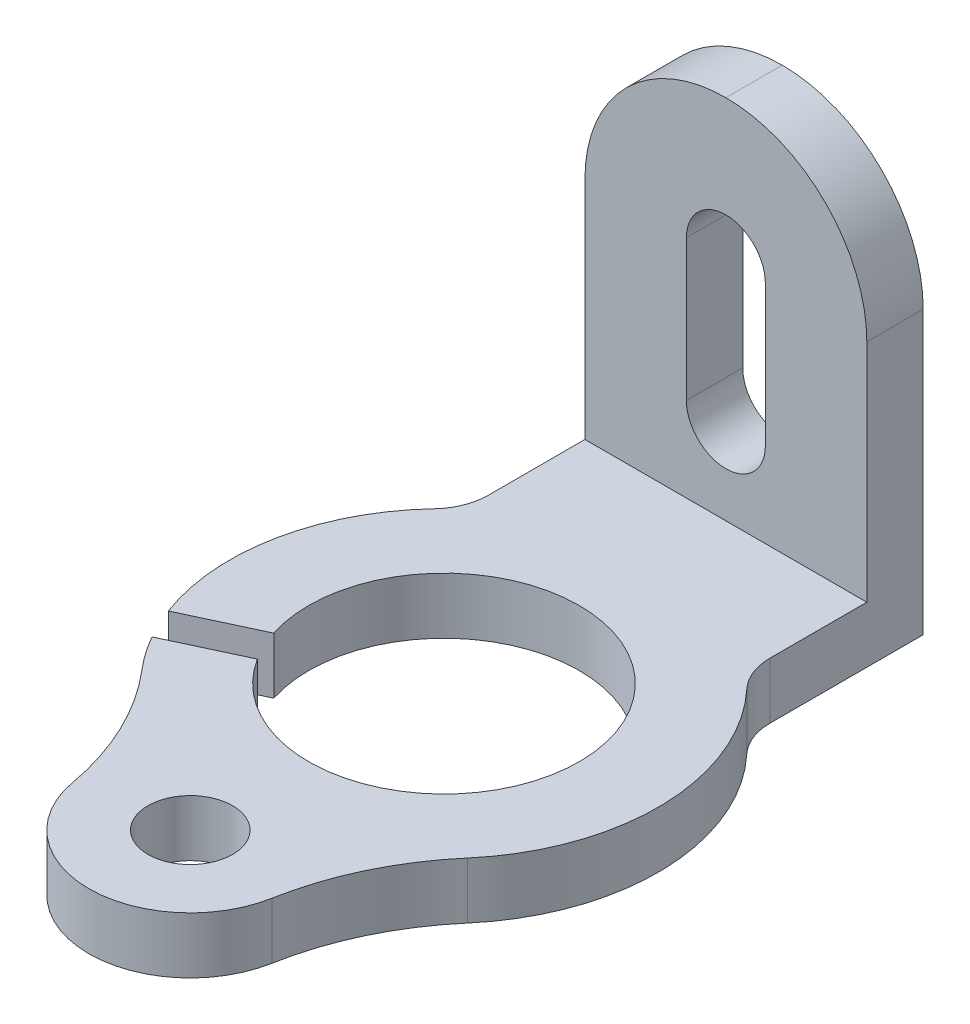
SolidWorks part; units mm, degrees
ref_plane "Front Plane" through (0, 0, 0) normal (0, 0, 1) x (1, 0, 0)
ref_plane "Top Plane" through (0, 0, 0) normal (0, 1, 0) x (1, 0, 0)
ref_plane "Right Plane" through (0, 0, 0) normal (1, 0, 0) x (0, 0, -1)
sketch "Sketch1" plane through (0, 0, 0) normal (0, 1, 0) x (1, 0, 0)
  line L0 (0, 0) -> (0, -117.5796) construction
  line L1 (25, 0) -> (-25, 0)
  line L2 (-25, 0) -> (-25, -17.1519)
  line L3 (0, -50) -> (-61.3292, -50) construction
  line L4 (0, -50) -> (-50.6583, -73.6224) construction
  line L5 (-35.6001, -63.2904) -> (-22.8486, -57.3444)
  line L6 (-33.0643, -68.7283) -> (-20.3129, -62.7822)
  line L7 (25, 0) -> (25, -17.1519)
  line L8 (-25, 0) -> (25, 0)
  line L9 (-25, 0) -> (-25, 10)
  line L10 (-25, 10) -> (25, 10)
  line L11 (25, 0) -> (25, 10)
  arc A0 (-20.3129, -62.7822) -> (-22.8486, -57.3444) centre (0, -50) ccw
  arc A1 (-33.0643, -68.7283) -> (-28.8898, -74.6856) centre (0, -50) ccw
  circle A2 centre (0, -95) radius 7.5
  arc A3 (-17.7095, -98.2206) -> (17.7095, -98.2206) centre (0, -95) ccw
  arc A4 (-27.7083, -23.9952) -> (-25, -17.1519) centre (-35, -17.1519) ccw
  arc A5 (-27.7083, -23.9952) -> (-35.6001, -63.2904) centre (0, -50) ccw
  arc A6 (-17.7095, -98.2206) -> (-28.8898, -74.6856) centre (-66.9027, -107.1667) ccw
  arc A7 (17.7095, -98.2206) -> (-17.7095, -98.2206) centre (0, -95) cw
  arc A8 (17.7095, -98.2206) -> (28.8898, -74.6856) centre (66.9027, -107.1667) cw
  arc A9 (33.0643, -68.7283) -> (28.8898, -74.6856) centre (0, -50) cw
  arc A10 (27.7083, -23.9952) -> (35.6001, -63.2904) centre (0, -50) cw
  arc A11 (27.7083, -23.9952) -> (25, -17.1519) centre (35, -17.1519) cw
  arc A12 (-33.0643, -68.7283) -> (-28.8898, -74.6856) centre (0, -50) ccw
  arc A13 (28.8898, -74.6856) -> (-35.6001, -63.2904) centre (0, -50) ccw
  point P12 (0, 0)
  point P26 (0, -113)
  dimension "D1" = 50
  dimension "D2" = 45
  dimension "D3" = 25
  dimension "D5" = 24
  dimension "D6" = 38
  dimension "D7" = 15
  dimension "D8" = 18
  dimension "D10" = 10
  dimension "D11" = 50
  dimension "D12" = 50
  dimension "D4" = 6
  dimension "D9" = 10
extrude "Boss-Extrude1" add sketch "Sketch1" along normal blind 10 contours A13 A11 L7 L1 L2 A4 | L1 L11 L10 L9 | A9 A13 A10 A5 L5 A0 L6 A1 A6 A3 A8 A2 region at (0, 0, 7.803) region at (0, 0, -5) region at (36.0168, 0, 42.7667)
extrude "Boss-Extrude2" add sketch "Sketch1<3>" along normal blind 75 contours L1 L11 L10 L9 region at (0, 0, -5)
sketch "Sketch1<3>" plane through (0, 0, 0) normal (0, 1, 0) x (1, 0, 0) same geometry as "Sketch1"
sketch "Sketch2" plane through (0, 0, 0) normal (0, 0, 1) x (1, 0, 0)
  line L0 (0, 50) -> (0, 25) construction
  line L1 (7, 50) -> (7, 25)
  line L2 (-7, 50) -> (-7, 25)
  line L3 (-17.7095, 0) -> (17.7095, 0) construction
  arc A0 (7, 50) -> (-7, 50) centre (0, 50) ccw
  arc A1 (-7, 25) -> (7, 25) centre (0, 25) ccw
  point P3 (0, 37.5)
  dimension "D3" = 7
  dimension "D1" = 25
  dimension "D2" = 50
extrude "Cut-Extrude1" cut sketch "Sketch2" against normal up to surface (10 mm away) up to face at (0, 37.5, -10)
fillet "Fillet1" radius 25 2 edges at (-25, 75, -5) (25, 75, -5)
